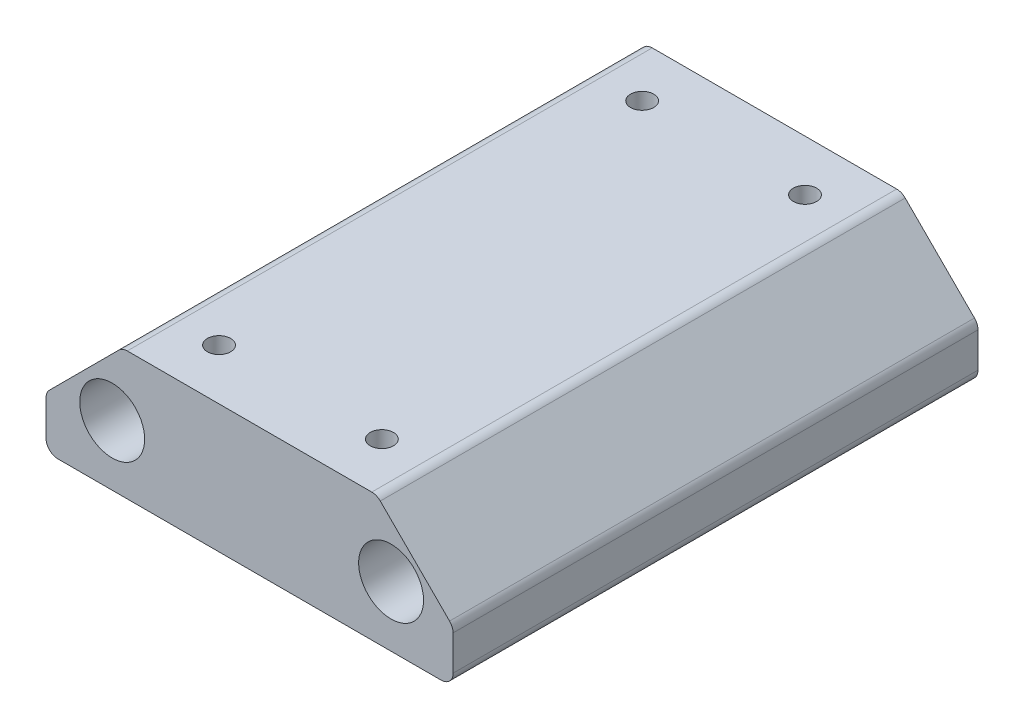
SolidWorks part; units mm, degrees
ref_plane "Front Plane" through (0, 0, 0) normal (0, 0, 1) x (1, 0, 0)
ref_plane "Top Plane" through (0, 0, 0) normal (0, 1, 0) x (1, 0, 0)
ref_plane "Right Plane" through (0, 0, 0) normal (1, 0, 0) x (0, 0, -1)
sketch "Sketch1" plane through (0, 0, 0) normal (0, 0, 1) x (1, 0, 0)
  line L1 (-25.6621, -156.15) -> (25.1379, -156.15)
  line L2 (-25.6621, -156.15) -> (-25.6621, -140.15)
  line L3 (-25.6621, -140.15) -> (25.1379, -140.15)
  line L4 (25.1379, -156.15) -> (25.1379, -140.15)
  circle A2 centre (-17.4, -148.6184) radius 4.05
  circle A3 centre (17.4, -148.6184) radius 4.05
  dimension "D1" = 16
  dimension "D2" = 50.8
extrude "Boss-Extrude1" add sketch "Sketch1" along normal up to surface (65.5 mm away)
fillet "Fillet1" radius 1.5 2 edges at (-25.6621, -156.15, 32.75) (25.1379, -156.15, 32.75)
chamfer "Chamfer1" distance 9.525 angle 45 2 edges at (25.1379, -140.15, 32.75) (-25.6621, -140.15, 32.75)
fillet "Fillet2" radius 1.5 4 edges at (25.1379, -149.675, 32.75) (15.6129, -140.15, 32.75) (-16.1371, -140.15, 32.75) (-25.6621, -149.675, 32.75)
sketch "Sketch3" plane through (0, -156.15, 0) normal (0, -1, 0) x (1, 0, 0)
  line L0 (-24.1621, 65.5) -> (23.6379, 65.5) construction
  line L1 (-10.4221, 59.15) -> (9.8979, 59.15) construction
  line L2 (-10.4221, 59.15) -> (-10.4221, 6.35) construction
  line L3 (-10.4221, 6.35) -> (9.8979, 6.35) construction
  line L4 (9.8979, 59.15) -> (9.8979, 6.35) construction
  line L5 (-24.1621, 0) -> (23.6379, 0) construction
  line L6 (25.1379, 65.5) -> (25.1379, 0) construction
  line L7 (-25.6621, 0) -> (-25.6621, 65.5) construction
  circle A0 centre (-10.4221, 59.15) radius 1.45
  circle A1 centre (9.8979, 59.15) radius 1.45
  circle A2 centre (-10.4221, 6.35) radius 1.45
  circle A3 centre (9.8979, 6.35) radius 1.45
  dimension "D1" = 2.9
  dimension "D2" = 6.35
  dimension "D3" = 6.35
  dimension "D4" = 15.24
  dimension "D5" = 15.24
extrude "Cut-Extrude1" cut sketch "Sketch3" against normal through all
